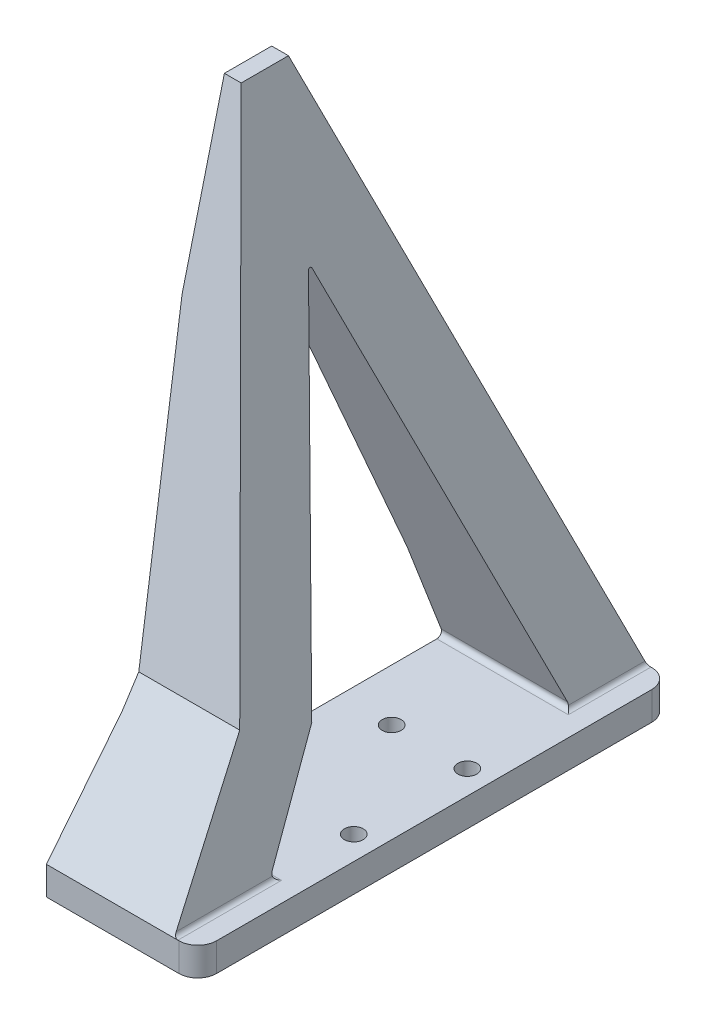
SolidWorks part; units mm, degrees
material "6061 合金"
ref_plane "前视基准面" through (0, 0, 0) normal (0, 0, 1) x (1, 0, 0)
ref_plane "上视基准面" through (0, 0, 0) normal (0, 1, 0) x (1, 0, 0)
ref_plane "右视基准面" through (0, 0, 0) normal (1, 0, 0) x (0, 0, -1)
sketch "草图1" plane through (0, 0, 0) normal (0, 1, 0) x (1, 0, 0)
  line L0 (2.75, 0) -> (0, 0) construction
  line L1 (-9.25, 25) -> (7.25, 25)
  line L2 (-9.25, 25) -> (-9.25, -25)
  line L3 (-9.25, -25) -> (7.25, -25)
  line L4 (9.25, 23) -> (9.25, -23)
  line L5 (-9.25, 25) -> (9.25, -25) construction
  line L6 (-9.25, -25) -> (9.25, 25) construction
  line L7 (-1.25, 6) -> (6.75, 6) construction
  line L8 (-1.25, 6) -> (-1.25, -6) construction
  line L9 (-1.25, -6) -> (6.75, -6) construction
  line L10 (6.75, 6) -> (6.75, -6) construction
  line L11 (-1.25, 6) -> (6.75, -6) construction
  line L12 (-1.25, -6) -> (6.75, 6) construction
  circle A0 centre (-1.25, 6) radius 1
  circle A1 centre (-1.25, -6) radius 1
  circle A2 centre (6.75, -6) radius 1
  circle A3 centre (6.75, 6) radius 1
  arc A5 (7.25, -25) -> (9.25, -23) centre (7.25, -23) ccw
  arc A6 (7.25, 25) -> (9.25, 23) centre (7.25, 23) cw
  point P0 (0, 0)
  point P6 (2.75, 0)
  dimension "D3" = 2
  dimension "D1" = 12
  dimension "D2" = 8
  dimension "D4" = 8
  dimension "D5" = 5
  dimension "D6" = 50
extrude "凸台-拉伸1" add sketch "草图1" along normal blind 3
sketch "草图2" plane through (0, 3, 0) normal (0, 1, 0) x (1, 0, 0)
  line L0 (-9.25, -25) -> (7.25, -25) construction
  line L1 (6.7578, -25) -> (-9.25, -25)
  line L2 (6.7578, -25) -> (6.7578, 25)
  line L3 (6.7578, 25) -> (-9.25, 25)
  line L4 (-9.25, -25) -> (-9.25, 25)
  line L5 (6.7578, -25) -> (-9.25, 25) construction
  line L6 (6.7578, 25) -> (-9.25, -25) construction
  point P0 (-1.2461, 0)
extrude "凸台-拉伸2" add sketch "草图2" along normal blind 80
sketch "草图3" plane through (6.7578, 0, 0) normal (1, 0, 0) x (0, 0, -1)
  line L0 (-25, 3) -> (-15, 15.5)
  line L1 (25, 3) -> (1.8182, 63)
  line L2 (0, 0) -> (0, 36.8077) construction
  line L3 (-15, 3) -> (-8, 13)
  line L4 (-8, 13) -> (0, 47)
  line L5 (-25, 3) -> (25, 3) construction
  line L6 (25, 0) -> (-25, 0) construction
  line L7 (1.8182, 63) -> (-3.1818, 63)
  line L8 (-3.1818, 63) -> (-15, 15.5)
  line L9 (0, 47) -> (17, 3)
  line L10 (-15, 3) -> (17, 3)
  line L11 (-25, 3) -> (-39.0868, 3)
  line L12 (-39.0868, 3) -> (-39.0868, 88.1336)
  line L13 (-39.0868, 88.1336) -> (32.7843, 88.1336)
  line L14 (32.7843, 88.1336) -> (32.7843, 3)
  line L15 (32.7843, 3) -> (25, 3)
  dimension "D1" = 10
  dimension "D2" = 15.5
  dimension "D3" = 15
  dimension "D4" = 8
  dimension "D5" = 13
  dimension "D6" = 47
  dimension "D7" = 8
  dimension "D8" = 5
  dimension "D9" = 60
extrude "切除-拉伸1" cut sketch "草图3" against normal through all
sketch "草图4" plane through (0, 0, 25) normal (0, 0, 1) x (1, 0, 0)
  line L0 (6.7578, 3) -> (6.7578, 67.7633)
  line L1 (6.7578, 67.7633) -> (-9.1496, 67.7633)
  line L2 (-9.1496, 67.7633) -> (6.7578, 3)
  dimension "D1" = 103.8
extrude "切除-拉伸2" cut sketch "草图4" against normal through all
sketch "草图5" plane through (-9.25, 0, 0) normal (-1, 0, 0) x (0, 0, 1)
  line L0 (0, 47) -> (-17, 3)
  line L1 (-17, 3) -> (15, 3)
  line L2 (15, 3) -> (8, 13)
  line L3 (8, 13) -> (0, 47)
  line L4 (-1.8182, 63) -> (-25, 3)
  line L5 (-25, 3) -> (-25, 0)
  line L6 (-25, 0) -> (25, 0)
  line L7 (25, 0) -> (25, 3)
  line L8 (25, 3) -> (15, 15.5)
  line L9 (15, 15.5) -> (3.1818, 63)
  line L10 (3.1818, 63) -> (-1.8182, 63)
extrude "凸台-拉伸3" add sketch "草图5" along normal blind 3
sketch "草图6" plane through (0, 0, -25) normal (0, 0, -1) x (-1, 0, 0)
  line L0 (6.75, 0) -> (6.75, 13)
  line L1 (-7.25, 0) -> (12.25, 0) construction
  line L2 (6.75, 13) -> (9.75, 45)
  line L3 (9.75, 45) -> (9.75, 64.871)
  line L4 (9.75, 64.871) -> (14.0936, 64.871)
  line L5 (14.0936, 64.871) -> (14.0936, 0)
  line L6 (14.0936, 0) -> (6.75, 0)
  line L7 (12.25, 13) -> (-4.3015, 13) construction
  line L8 (12.25, 63) -> (12.25, 3) construction
  line L9 (12.25, 63) -> (7.9797, 63) construction
  dimension "D1" = 5.5
  dimension "D2" = 2.5
  dimension "D3" = 18
extrude "切除-拉伸3" cut sketch "草图6" against normal through all
fillet "圆角1" radius 0.5 4 edges at (6.7578, 3, -21) (6.7578, 3, 20) (0.0039, 3, -17) (0.0039, 3, 15)
fillet "圆角2" radius 0.2 1 edges at (-6.8998, 47, 0)
